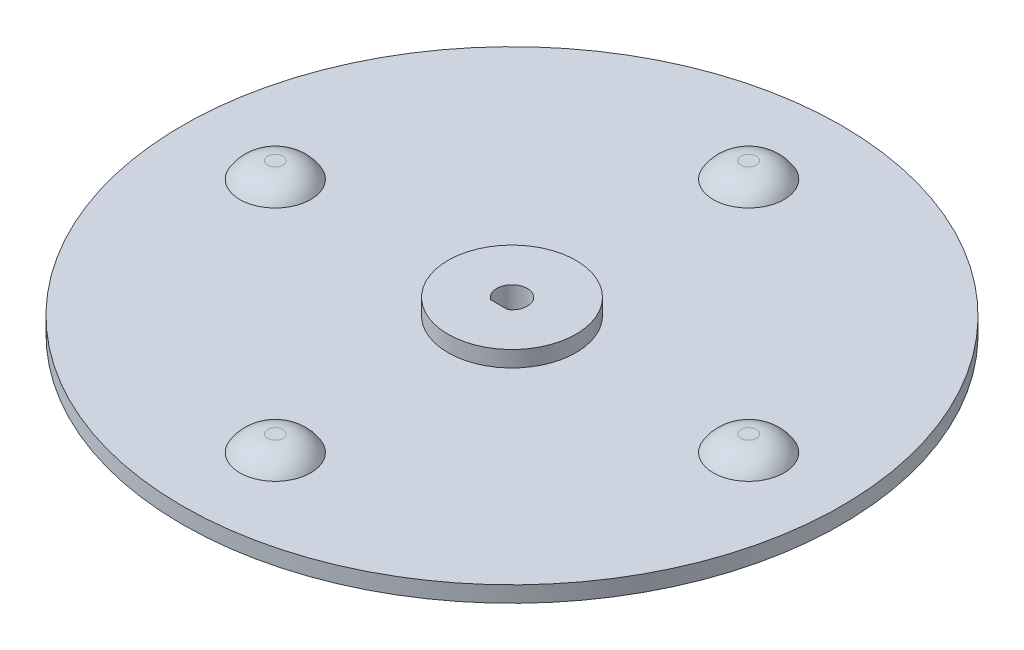
SolidWorks part; units mm, degrees
ref_plane "Front Plane" through (0, 0, 0) normal (0, 0, 1) x (1, 0, 0)
ref_plane "Top Plane" through (0, 0, 0) normal (0, 1, 0) x (1, 0, 0)
ref_plane "Right Plane" through (0, 0, 0) normal (1, 0, 0) x (0, 0, -1)
sketch "Sketch1" plane through (0, 0, 0) normal (0, 1, 0) x (1, 0, 0)
  circle A0 centre (0, 0) radius 65.405
  dimension "D1" = 130.81
extrude "Boss-Extrude1" add sketch "Sketch1" along normal blind 3.175
sketch "Sketch2" plane through (0, 3.175, 0) normal (0, 1, 0) x (1, 0, 0)
  circle A0 centre (0, 0) radius 12.7
  dimension "D1" = 25.4
extrude "Boss-Extrude2" add sketch "Sketch2" along normal blind 3.175
sketch "Sketch3" plane through (0, 6.35, 0) normal (0, 1, 0) x (1, 0, 0)
  line L1 (-1.6848, -2.54) -> (1.6848, -2.54)
  arc A0 (1.6848, -2.54) -> (-1.6848, -2.54) centre (0, 0) ccw
  point P1 (0, 0)
  dimension "D1" = 6.096
extrude "Cut-Extrude1" cut sketch "Sketch3" against normal blind 5.842
sketch "Sketch4" plane through (0, 3.175, 0) normal (0, 1, 0) x (1, 0, 0)
  circle A1 centre (0, 46.9731) radius 7.0323
  circle A2 centre (46.9731, 0) radius 7.0323
  circle A3 centre (0, -46.9731) radius 7.0323
  circle A4 centre (-46.9731, 0) radius 7.0323
  point P14 (0, 0)
  dimension "D1" = 4
extrude "Boss-Extrude3" add sketch "Sketch4" along normal blind 3.175
fillet "Fillet3" radius 6.35 4 edges at (46.9731, 6.35, 7.0323) (0, 6.35, -39.9409) (-46.9731, 6.35, 7.0323) (0, 6.35, 54.0054)
